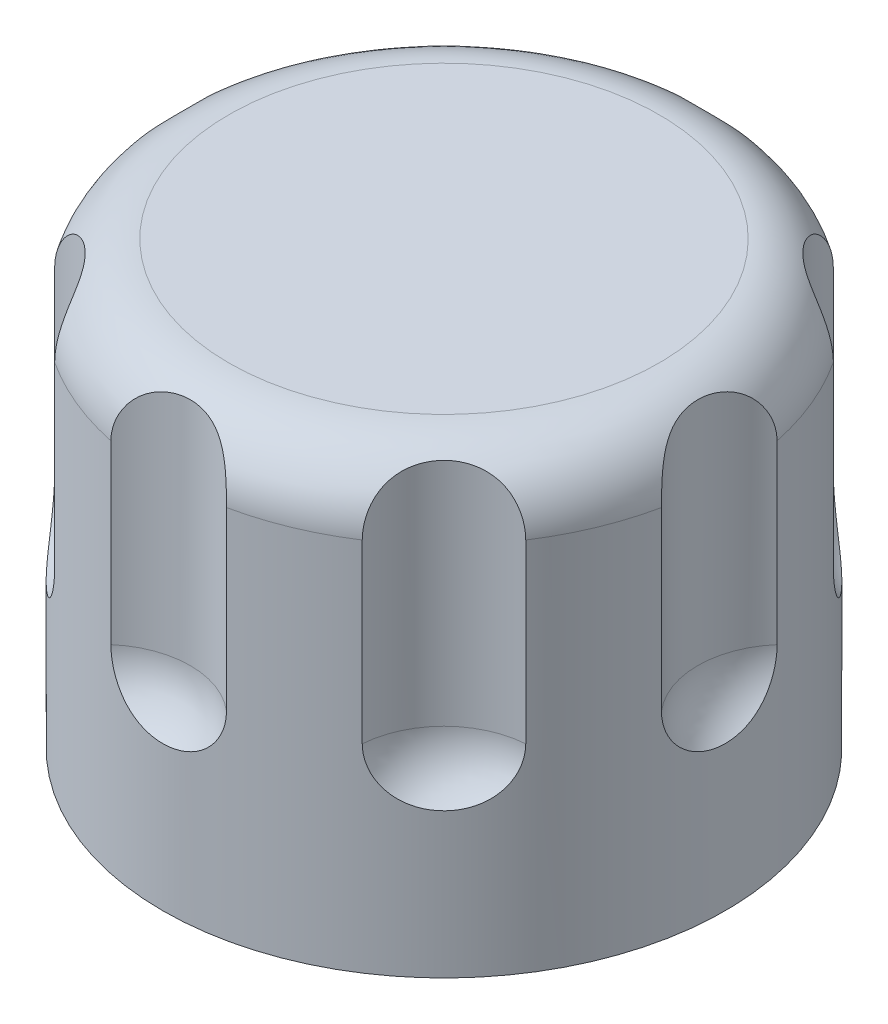
SolidWorks part; units mm, degrees
ref_plane "Front Plane" through (0, 0, 0) normal (0, 0, 1) x (1, 0, 0)
ref_plane "Top Plane" through (0, 0, 0) normal (0, 1, 0) x (1, 0, 0)
ref_plane "Right Plane" through (0, 0, 0) normal (1, 0, 0) x (0, 0, -1)
sketch "Sketch1" plane through (0, 0, 0) normal (0, 1, 0) x (1, 0, 0)
  circle A0 centre (0, 0) radius 12.75
  dimension "D1" = 25.5
extrude "Boss-Extrude1" add sketch "Sketch1" along normal blind 20
sketch "Sketch2" plane through (0, 0, 0) normal (0, -1, 0) x (1, 0, 0)
  circle A0 centre (0, 0) radius 3.05
  dimension "D1" = 6.1
extrude "Cut-Extrude1" cut sketch "Sketch2" against normal blind 18.3 and the other way through all
sketch "Sketch3" plane through (0, 0, 0) normal (0, -1, 0) x (1, 0, 0)
  circle A0 centre (0, 0) radius 3.5
  dimension "D1" = 7
extrude "Cut-Extrude2" cut sketch "Sketch3" against normal blind 6
fillet "Fillet1" radius 3 1 edges at (0, 20, 12.75)
sketch "Sketch5" plane through (0, 20, 0) normal (0, 1, 0) x (1, 0, 0)
  circle A2 centre (0, 15.5) radius 4
  circle A3 centre (0, 0) radius 12.75 construction
  circle A4 centre (10.9602, 10.9602) radius 4
  circle A5 centre (15.5, 0) radius 4
  circle A6 centre (10.9602, -10.9602) radius 4
  circle A7 centre (0, -15.5) radius 4
  circle A8 centre (-10.9602, -10.9602) radius 4
  circle A9 centre (-15.5, 0) radius 4
  circle A10 centre (-10.9602, 10.9602) radius 4
  point P5 (2.291, 0)
  point P20 (0, 0)
  dimension "D1" = 8
  dimension "D3" = 0
  dimension "D5" = 0
  dimension "D2" = 15.5
  dimension "D4" = 8
extrude "Cut-Extrude3" cut sketch "Sketch5" against normal blind 14
fillet "Fillet3" radius 3 8 edges at (0, 6, 11.5) (-8.1317, 6, 8.1317) (-11.5, 6, 0) (-8.1317, 6, -8.1317) (0, 6, -11.5) (8.1317, 6, -8.1317) (11.5, 6, 0) (8.1317, 6, 8.1317)
